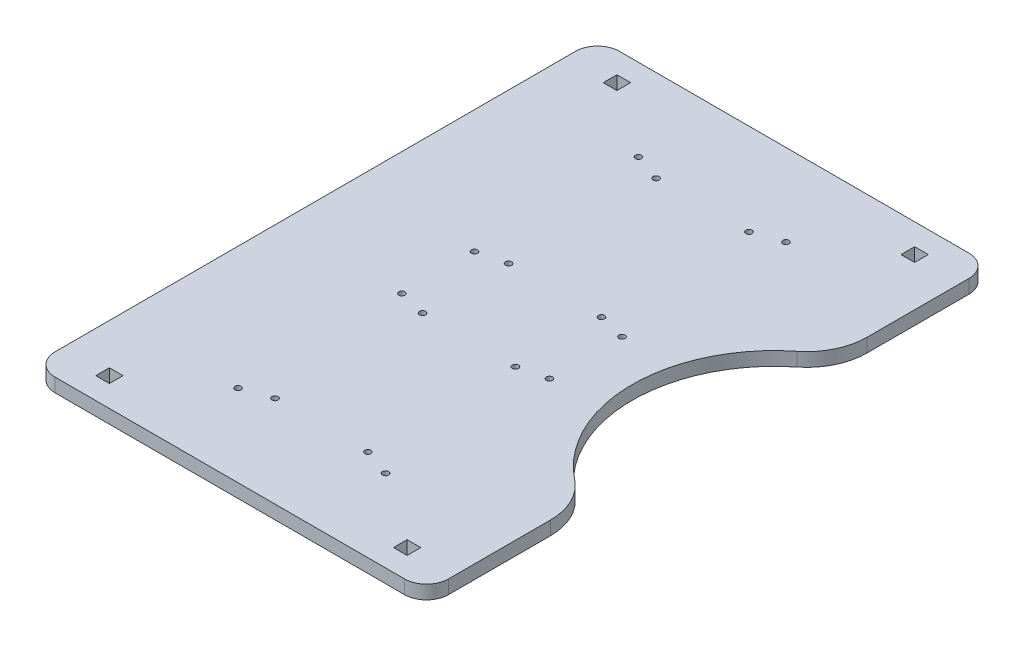
SolidWorks part; units mm, degrees
ref_plane "Front Plane" through (0, 0, 0) normal (0, 0, 1) x (1, 0, 0)
ref_plane "Top Plane" through (0, 0, 0) normal (0, 1, 0) x (1, 0, 0)
ref_plane "Right Plane" through (0, 0, 0) normal (1, 0, 0) x (0, 0, -1)
sketch "Sketch3" plane through (0, 0, 0) normal (0, 1, 0) x (1, 0, 0)
  line L4 (182.88, 0) -> (0, 0)
  line L5 (91.44, 262.3393) -> (91.44, 0) construction
  line L6 (19.05, 16.3877) -> (25.4, 16.3877)
  line L7 (19.05, 16.3877) -> (19.05, 10.0377)
  line L8 (19.05, 10.0377) -> (25.4, 10.0377)
  line L9 (25.4, 16.3877) -> (25.4, 10.0377)
  line L10 (163.83, 10.0377) -> (157.48, 10.0377)
  line L11 (157.48, 16.3877) -> (157.48, 10.0377)
  line L12 (163.83, 16.3877) -> (157.48, 16.3877)
  line L13 (163.83, 16.3877) -> (163.83, 10.0377)
  line L14 (0, 0) -> (0, 262.3393)
  line L15 (0, 262.3393) -> (182.88, 262.3393)
  line L16 (182.88, 262.3393) -> (182.88, 189.7551)
  line L17 (0, 131.1696) -> (182.88, 131.1696) construction
  line L18 (163.83, 245.9515) -> (163.83, 252.3015)
  line L19 (163.83, 245.9515) -> (157.48, 245.9515)
  line L20 (157.48, 245.9515) -> (157.48, 252.3015)
  line L21 (163.83, 252.3015) -> (157.48, 252.3015)
  line L22 (19.05, 252.3015) -> (25.4, 252.3015)
  line L23 (25.4, 245.9515) -> (25.4, 252.3015)
  line L24 (19.05, 245.9515) -> (25.4, 245.9515)
  line L25 (19.05, 245.9515) -> (19.05, 252.3015)
  line L26 (182.88, 72.5842) -> (182.88, 0)
  circle A6 centre (57.15, 38.1) radius 1.4224
  circle A7 centre (57.15, 114.3) radius 1.4224
  circle A8 centre (125.73, 114.3) radius 1.4224
  circle A9 centre (125.73, 38.1) radius 1.4224
  circle A10 centre (69.85, 151.1577) radius 1.4224
  circle A11 centre (69.85, 219.7377) radius 1.4224
  circle A12 centre (113.03, 151.1577) radius 1.4224
  circle A13 centre (113.03, 219.7377) radius 1.4224
  circle A14 centre (113.03, 42.6016) radius 1.4224
  circle A15 centre (113.03, 111.1816) radius 1.4224
  circle A16 centre (69.85, 111.1816) radius 1.4224
  circle A17 centre (69.85, 42.6016) radius 1.4224
  circle A18 centre (125.73, 148.0393) radius 1.4224
  circle A19 centre (125.73, 224.2393) radius 1.4224
  circle A20 centre (57.15, 224.2393) radius 1.4224
  circle A21 centre (57.15, 148.0393) radius 1.4224
  arc A22 (182.88, 189.7551) -> (182.88, 72.5842) centre (213.36, 131.1696) ccw
  dimension "D2" = 19.05
  dimension "D3" = 30.48
  dimension "D10" = 38.1
  dimension "D13" = 68.58
  dimension "D4" = 19.05
  dimension "D5" = 182.88
  dimension "D6" = 6.35
  dimension "D7" = 6.35
  dimension "D11" = 76.2
  dimension "D12" = 68.58
  dimension "D14" = 43.18
extrude "Boss-Extrude1" add sketch "Sketch3" along normal blind 6.35
fillet "Fillet1" radius 10.16 4 edges at (0, 3.175, 0) (0, 3.175, -262.3393) (182.88, 3.175, -262.3393) (182.88, 3.175, 0)
fillet "Fillet2" radius 27.94 2 edges at (182.88, 3.175, -189.7551) (182.88, 3.175, -72.5842)
